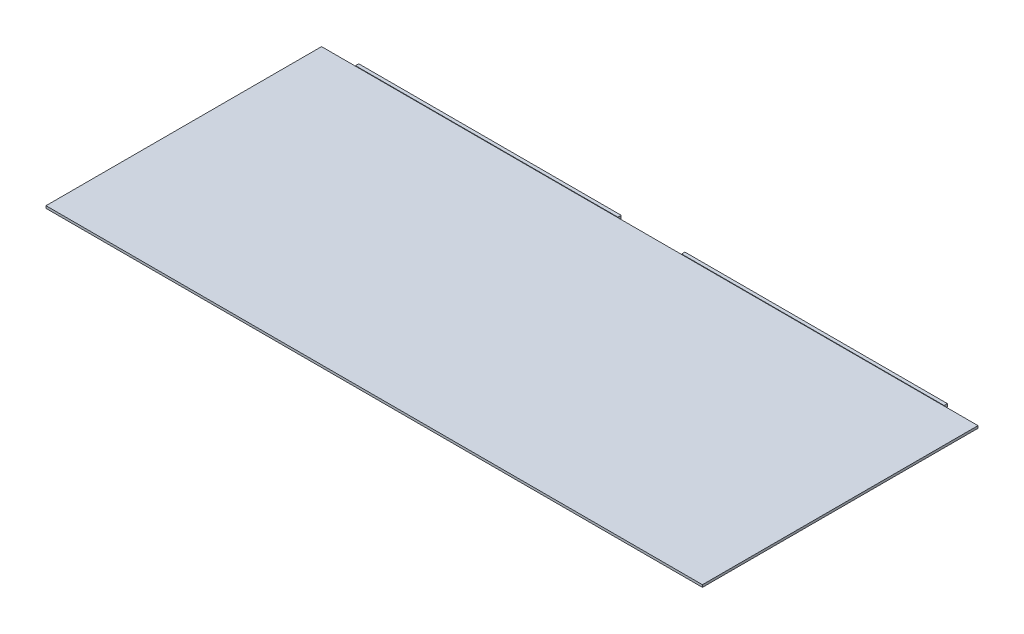
SolidWorks part; units mm, degrees
material "6061-T6 (SS)"
ref_plane "X-Y Datum" through (0, 0, 0) normal (0, 0, 1) x (1, 0, 0)
ref_plane "X-Z Datum" through (0, 0, 0) normal (0, 1, 0) x (1, 0, 0)
ref_plane "Y-Z Datum" through (0, 0, 0) normal (1, 0, 0) x (0, 0, -1)
sketch "Sketch1" plane through (0, 0, 0) normal (0, 1, 0) x (1, 0, 0)
  line L1 (-317.6778, 133.35) -> (317.6778, 133.35)
  line L2 (-317.6778, 133.35) -> (-317.6778, -133.35)
  line L3 (-317.6778, -133.35) -> (317.6778, -133.35)
  line L4 (317.6778, 133.35) -> (317.6778, -133.35)
  line L5 (-317.6778, 133.35) -> (317.6778, -133.35) construction
  line L6 (-317.6778, -133.35) -> (317.6778, 133.35) construction
  point P0 (0, 0)
  dimension "D1" = 635.3556
  dimension "D2" = 266.7
extrude "Boss-Extrude1" add sketch "Sketch1" along normal mid plane 2.286
sketch "Sketch2" plane through (0, 0, -133.35) normal (0, 0, -1) x (-1, 0, 0)
  line L20 (-317.6778, -1.143) -> (317.6778, -1.143) construction
  line L21 (-284.8229, -1.143) -> (-30.8229, -1.143)
  line L22 (30.8229, -1.143) -> (284.8229, -1.143)
  line L40 (30.8229, -1.143) -> (30.8229, 1.5875)
  line L41 (30.8229, 1.5875) -> (284.8229, 1.5875)
  line L42 (284.8229, 1.5875) -> (284.8229, -1.143)
  line L56 (-284.8229, -1.143) -> (-284.8229, 1.5875)
  line L57 (-284.8229, 1.5875) -> (-30.8229, 1.5875)
  line L58 (-30.8229, 1.5875) -> (-30.8229, -1.143)
extrude "Boss-Extrude2" add sketch "Sketch2" along normal blind 3.175
